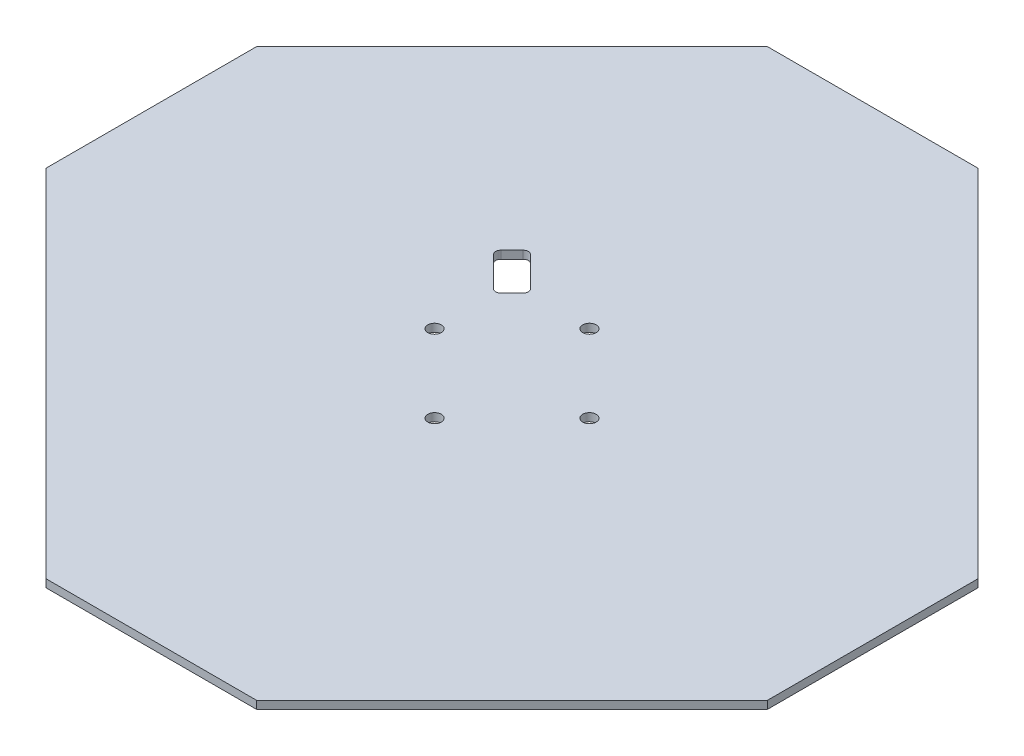
SolidWorks part; units mm, degrees
ref_plane "Front Plane" through (0, 0, 0) normal (0, 0, 1) x (1, 0, 0)
ref_plane "Top Plane" through (0, 0, 0) normal (0, 1, 0) x (1, 0, 0)
ref_plane "Right Plane" through (0, 0, 0) normal (1, 0, 0) x (0, 0, -1)
sketch "Sketch1" plane through (0, 0, 0) normal (0, 1, 0) x (1, 0, 0)
  line L0 (0, 0) -> (-88.7419, -88.7419) construction
  line L1 (68.75, -165.9772) -> (165.9772, -68.75) construction
  line L2 (165.9772, -68.75) -> (165.9772, 68.75) construction
  line L3 (165.9772, 68.75) -> (68.75, 165.9772) construction
  line L4 (68.75, 165.9772) -> (-68.75, 165.9772) construction
  line L5 (-68.75, 165.9772) -> (-165.9772, 68.75) construction
  line L6 (-165.9772, 68.75) -> (-165.9772, -68.75) construction
  line L7 (-165.9772, -68.75) -> (-68.75, -165.9772) construction
  line L8 (-68.75, -165.9772) -> (68.75, -165.9772) construction
  line L9 (117.3636, 117.3636) -> (-117.3636, -117.3636) construction
  line L10 (0, 0) -> (88.7419, 88.7419) construction
  line L11 (-88.7419, -88.7419) -> (-11.5066, -165.9772) construction
  line L12 (-11.5066, -165.9772) -> (-165.9772, -11.5066) construction
  line L13 (88.7419, 88.7419) -> (165.9772, 11.5066) construction
  line L14 (165.9772, 11.5066) -> (11.5066, 165.9772) construction
  circle A0 centre (0, 0) radius 165.9772 construction
  dimension "D1" = 137.5
sketch "Sketch3" plane through (0, 0, 0) normal (0, 1, 0) x (1, 0, 0)
  line L3 (146.9176, 30.5662) -> (11.5066, 165.9772)
  line L4 (11.5066, 165.9772) -> (-68.75, 165.9772)
  line L5 (-68.75, 165.9772) -> (-165.9772, 68.75)
  line L6 (-165.9772, 68.75) -> (-165.9772, -11.5066)
  line L7 (-165.9772, -11.5066) -> (-30.5662, -146.9176)
  line L8 (-68.75, 165.9772) -> (146.9176, -49.6904) construction
  line L9 (-165.9772, 68.75) -> (49.6904, -146.9176) construction
  line L10 (49.6904, -146.9176) -> (146.9176, -49.6904)
  line L11 (146.9176, 30.5662) -> (146.9176, -49.6904)
  line L12 (49.6904, -146.9176) -> (-30.5662, -146.9176)
extrude "Boss-Extrude2" add sketch "Sketch3" along normal blind 3
hole_wizard "13/64 (0.20313) Diameter Hole1" positions "Sketch8" profile "Sketch7" hole size "13/64" standard "ANSI Inch" end condition up to next
sketch "Sketch8" plane through (0, 0, 0) normal (0, -1, 0) x (-1, 0, 0)
  point P0 (39.0298, 9.5282)
  point P3 (9.5282, -19.9702)
  point P6 (-19.9702, 9.5314)
  point P9 (9.5314, 39.0298)
  point P12 (0, 0)
  point P13 (0, 0)
  point P14 (0, 0)
  point P15 (0, 0)
  point P16 (0, 0)
  point P17 (0, 0)
  point P18 (0, 0)
sketch "Sketch7" plane through (-39.0298, 0, -9.5282) normal (1, 0, 0) x (0, 0, -1)
  line L0 (0, 0) -> (0, 3)
  line L1 (0, 3) -> (2.5798, 3)
  line L2 (2.5798, 3) -> (2.5798, 0)
  line L5 (2.5798, 0) -> (0, 0)
  line L11 (0, -6.35) -> (0, 107.95) construction
  dimension "Thru Hole Dia." = 5.1595
  dimension "Thru Hole Depth" = 3
sketch "Sketch11" plane through (0, 0, 0) normal (0, -1, 0) x (-1, 0, 0)
  line L0 (98.2717, -79.2121) -> (-79.2121, 98.2717)
  line L1 (165.9772, -11.5066) -> (30.5662, -146.9176) construction
  line L2 (-146.9176, 30.5662) -> (-11.5066, 165.9772) construction
  line L3 (-79.2121, 98.2717) -> (9.5298, 9.5298)
  line L4 (9.5298, 9.5298) -> (36.0463, 36.0463)
  point P8 (0, 0)
sketch "Sketch12" plane through (0, 0, 0) normal (0, -1, 0) x (1, 0, 0)
  line L0 (-9.5298, -9.5298) -> (-36.0463, -36.0463) construction
  line L1 (-36.0463, -36.0463) -> (-39.5818, -32.5108)
  line L2 (-36.0463, -36.0463) -> (-32.5108, -39.5818)
  line L3 (-32.5108, -39.5818) -> (-46.6529, -53.724)
  line L4 (-46.6529, -53.724) -> (-53.724, -46.6529)
  line L5 (-53.724, -46.6529) -> (-39.5818, -32.5108)
extrude "Cut-Extrude1" cut sketch "Sketch12" against normal through all
fillet "Fillet2" radius 2 1 edges at (-39.5818, 1.5, -32.5108) type face fillet first side face at (-46.6529, 1.5, -39.5818) second side face at (-36.0463, 1.5, -36.0463)
fillet "Fillet3" radius 2 1 edges at (-32.5108, 1.5, -39.5818) type face fillet first side face at (-35.3392, 1.5, -36.7534) second side face at (-39.5818, 1.5, -46.6529)
fillet "Fillet4" radius 2 1 edges at (-53.724, 1.5, -46.6529) type face fillet first side face at (-47.36, 1.5, -40.289) second side face at (-50.1884, 1.5, -50.1884)
fillet "Fillet5" radius 2 1 edges at (-46.6529, 1.5, -53.724) type face fillet first side face at (-40.289, 1.5, -47.36) second side face at (-49.4813, 1.5, -50.8956)
